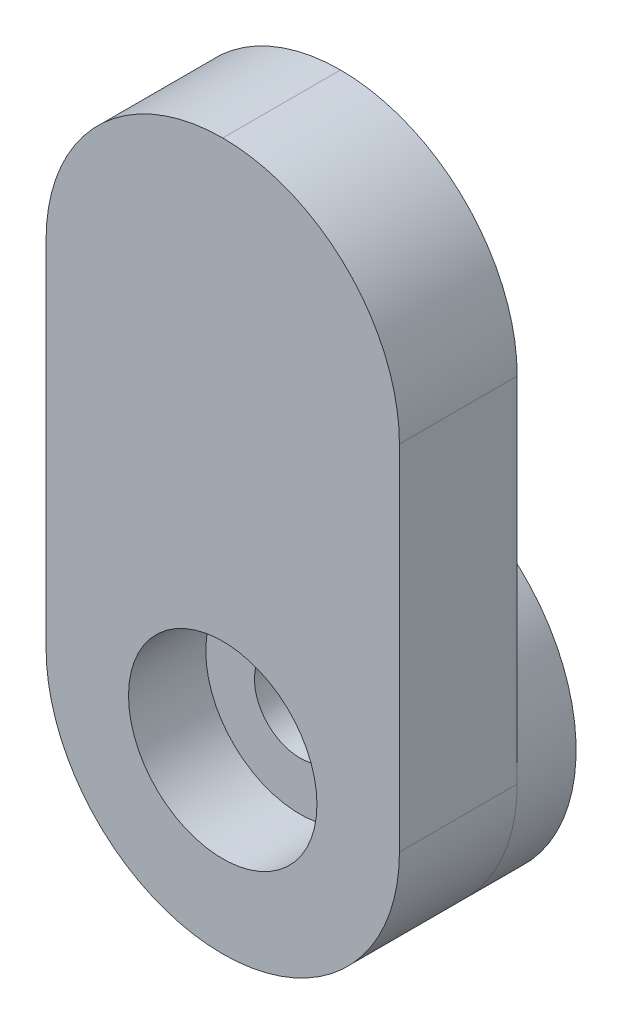
SolidWorks part; units mm, degrees
ref_plane "Front Plane" through (0, 0, 0) normal (0, 0, 1) x (1, 0, 0)
ref_plane "Top Plane" through (0, 0, 0) normal (0, 1, 0) x (1, 0, 0)
ref_plane "Right Plane" through (0, 0, 0) normal (1, 0, 0) x (0, 0, -1)
sketch "Sketch1" plane through (0, 0, 0) normal (0, 0, 1) x (1, 0, 0)
  line L1 (-9.525, 38.1) -> (9.525, 38.1)
  line L2 (-9.525, 38.1) -> (-9.525, 0)
  line L3 (-9.525, 0) -> (9.525, 0)
  line L4 (9.525, 38.1) -> (9.525, 0)
  line L5 (-9.525, 38.1) -> (9.525, 0) construction
  line L6 (-9.525, 0) -> (9.525, 38.1) construction
  point P0 (0, 19.05)
  dimension "D1" = 19.05
  dimension "D2" = 38.1
extrude "Boss-Extrude1" add sketch "Sketch1" along normal blind 6.35
hole_wizard "CBORE for #8 Socket Head Cap Screw1" positions "Sketch2" profile "Sketch3" counterbore size "#8" standard "ANSI Inch" end condition through all
sketch "Sketch2" plane through (0, 0, 6.35) normal (0, 0, 1) x (1, 0, 0)
  line L0 (-9.525, 0) -> (9.525, 0) construction
  point P0 (0, 9.525)
  dimension "D1" = 9.525
sketch "Sketch3" plane through (0, 9.525, 6.35) normal (1, 0, 0) x (0, -1, 0)
  line L0 (0, 0) -> (0, 6.35)
  line L1 (0, 6.35) -> (2.4575, 6.35)
  line L3 (2.4575, 6.35) -> (2.4575, 4.1656)
  line L4 (2.4575, 4.1656) -> (5.08, 4.1656)
  line L5 (5.08, 4.1656) -> (5.08, 0)
  line L7 (5.08, 0) -> (0, 0)
  line L11 (0, -6.35) -> (0, 107.95) construction
  dimension "Thru Hole Dia." = 4.9149
  dimension "Thru Hole Depth" = 6.35
  dimension "C'Bore Dia." = 10.16
  dimension "C'Bore Depth" = 4.1656
sketch "Sketch4" plane through (0, 0, 0) normal (0, 0, -1) x (-1, 0, 0)
  circle A0 centre (0, 9.525) radius 2.4575
  circle A1 centre (0, 9.525) radius 9.525
  circle A2 centre (0, 9.525) radius 2.4575 construction
  dimension "D1" = 19.05
extrude "Boss-Extrude2" add sketch "Sketch4" along normal blind 3.175
sketch "Sketch5" plane through (0, 0, -3.175) normal (0, 0, -1) x (-1, 0, 0)
  line L0 (-3.6422, 14.7266) -> (-1.4095, 11.538)
  line L1 (1.4095, 11.538) -> (3.6422, 14.7266)
  line L2 (0, 11.9825) -> (0, 15.875) construction
  line L3 (0, 9.525) -> (-1.4095, 11.538) construction
  line L4 (0, 9.525) -> (1.4095, 11.538) construction
  arc A0 (3.6422, 14.7266) -> (-3.6422, 14.7266) centre (0, 9.525) ccw
  arc A1 (1.4095, 11.538) -> (-1.4095, 11.538) centre (0, 9.525) ccw
  circle A2 centre (0, 9.525) radius 2.4575 construction
  dimension "D1" = 12.7
  dimension "D2" = 35
extrude "Boss-Extrude3" add sketch "Sketch5" along normal blind 2.54
fillet "Fillet1" radius 9.525 4 edges at (9.525, 38.1, 3.175) (-9.525, 38.1, 3.175) (9.525, 0, 3.175) (-9.525, 0, 3.175)
